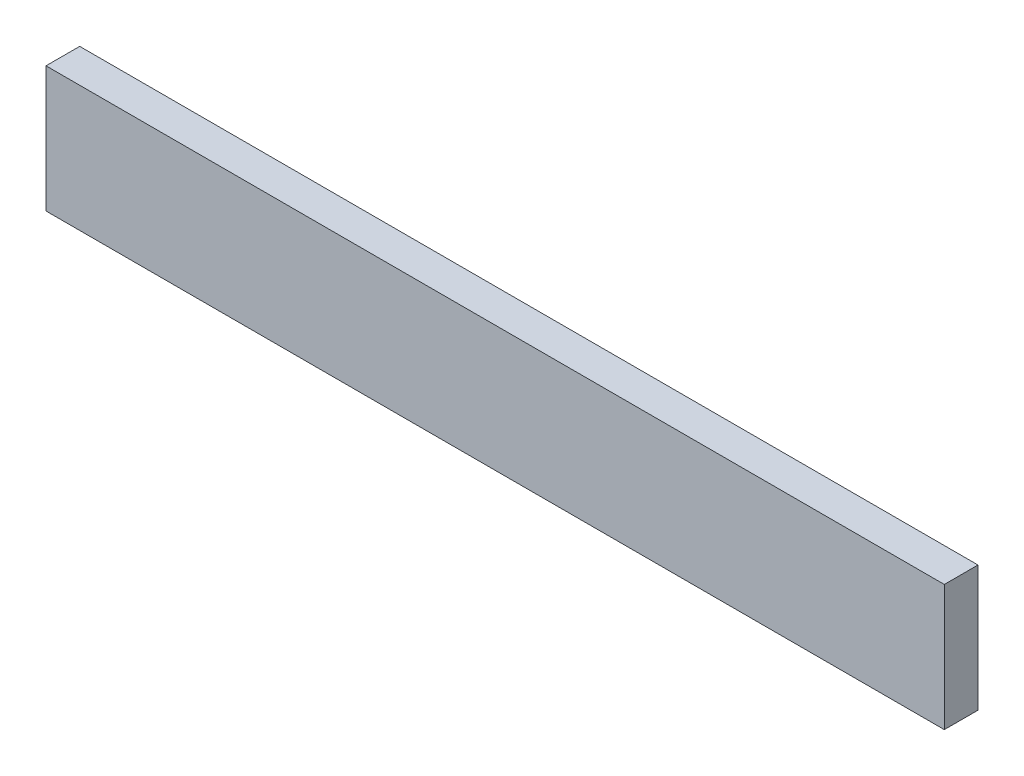
SolidWorks part; units mm, degrees
ref_plane "Front Plane" through (0, 0, 0) normal (0, 0, 1) x (1, 0, 0)
ref_plane "Top Plane" through (0, 0, 0) normal (0, 1, 0) x (1, 0, 0)
ref_plane "Right Plane" through (0, 0, 0) normal (1, 0, 0) x (0, 0, -1)
sketch "Sketch1" plane through (0, 0, 0) normal (0, 0, 1) x (1, 0, 0)
  line L1 (0, 0) -> (80, 0)
  line L2 (0, 0) -> (0, -11.2)
  line L3 (0, -11.2) -> (80, -11.2)
  line L4 (80, 0) -> (80, -11.2)
sketch "Sketch2" plane through (0, 0, 0) normal (1, 0, 0) x (0, 0, -1)
  line L1 (0, 0) -> (-3, 0)
  line L2 (0, 0) -> (0, -11.2)
  line L3 (0, -11.2) -> (-3, -11.2)
  line L4 (-3, 0) -> (-3, -11.2)
extrude "Boss-Extrude1" add sketch "Sketch1" along normal up to vertex (3 mm away) up to point (0, -11.2, 3)
